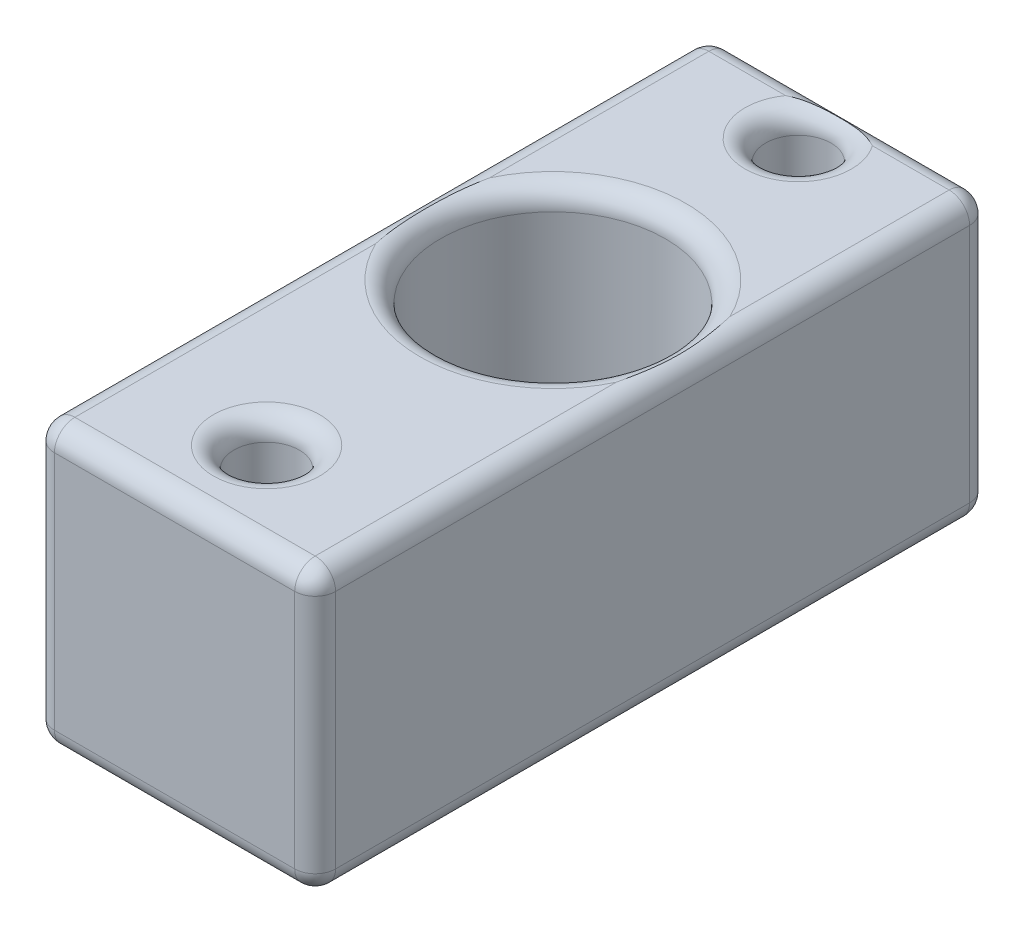
SolidWorks part; units mm, degrees
ref_plane "Front Plane" through (0, 0, 0) normal (0, 0, 1) x (1, 0, 0)
ref_plane "Top Plane" through (0, 0, 0) normal (0, 1, 0) x (1, 0, 0)
ref_plane "Right Plane" through (0, 0, 0) normal (1, 0, 0) x (0, 0, -1)
sketch "Sketch1" plane through (0, 0, 0) normal (0, 0, 1) x (1, 0, 0)
  line L1 (-6.875, -6.875) -> (6.875, -6.875)
  line L2 (-6.875, -6.875) -> (-6.875, 6.875)
  line L3 (-6.875, 6.875) -> (6.875, 6.875)
  line L4 (6.875, -6.875) -> (6.875, 6.875)
  line L5 (-6.875, -6.875) -> (6.875, 6.875) construction
  line L6 (-6.875, 6.875) -> (6.875, -6.875) construction
  point P0 (0, 0)
  dimension "D1" = 13.75
extrude "Boss-Extrude1" add sketch "Sketch1" along normal blind 18 and the other way blind 15
sketch "Sketch2" plane through (0, 0, 0) normal (0, 1, 0) x (1, 0, 0)
  circle A6 centre (0, 12.5) radius 1.6 construction
  circle A7 centre (0, 12.5) radius 1.6
  circle A8 centre (0, -13.5) radius 1.6 construction
  circle A9 centre (0, 0.5) radius 5.5 construction
  circle A10 centre (0, -13.5) radius 1.6
  circle A11 centre (0, 0.5) radius 5.5
extrude "Cut-Extrude1" cut sketch "Sketch2" against normal blind 10 and the other way blind 10
fillet "Fillet1" radius 1 18 edges at (0, 6.875, -15) (-6.875, 0, -15) (0, -6.875, -15) (6.875, 0, -15) (0, -6.875, 18) (-6.875, 0, 18) (0, 6.875, 18) (6.875, 0, 18) (0, -6.875, 11.9) (0, -6.875, -14.1) (0, 6.875, 15.1) (0, 6.875, -10.9) (0, 6.875, 5) (0, -6.875, -6) (6.875, -6.875, 1.5) (6.875, 6.875, 1.5) (-6.875, 6.875, 1.5) (-6.875, -6.875, 1.5)
